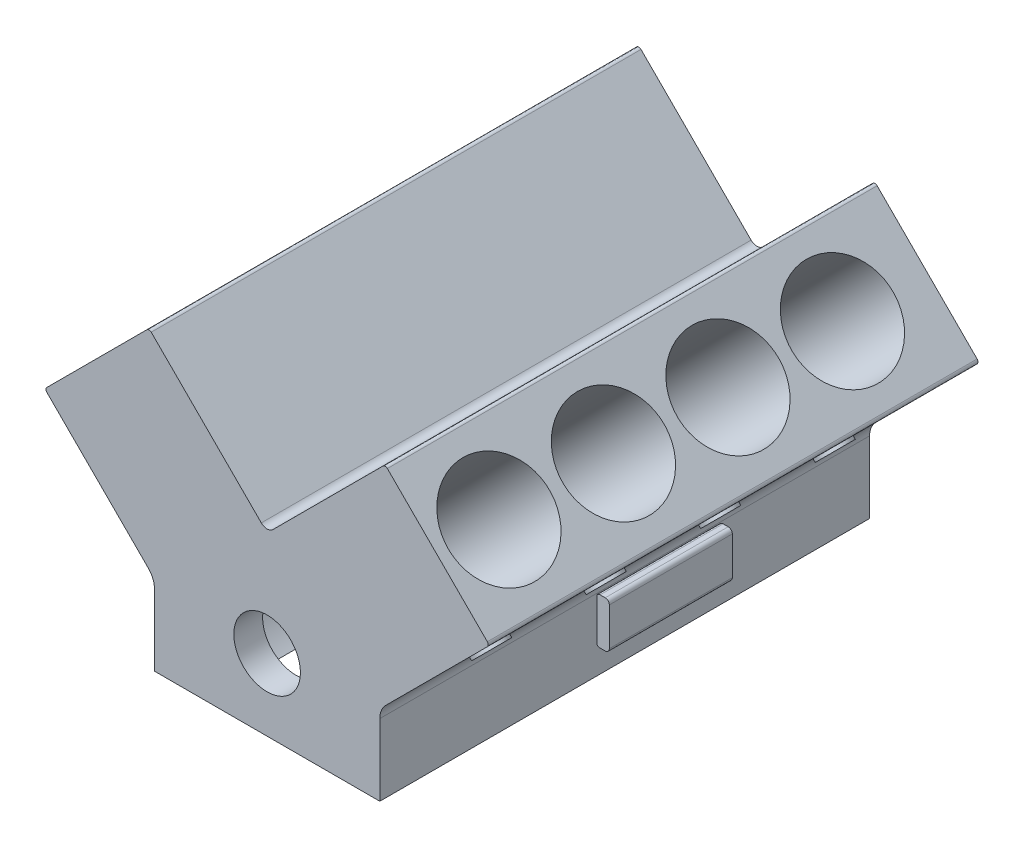
SolidWorks part; units mm, degrees
ref_plane "Front Plane" through (0, 0, 0) normal (0, 0, 1) x (1, 0, 0)
ref_plane "Top Plane" through (0, 0, 0) normal (0, 1, 0) x (1, 0, 0)
ref_plane "Right Plane" through (0, 0, 0) normal (1, 0, 0) x (0, 0, -1)
other "Configuration Table"
sketch "Sketch1" plane through (0, 0, 0) normal (0, 0, 1) x (1, 0, 0)
  line L0 (110, -70) -> (110, -0.1076)
  line L1 (115.8579, 14.0345) -> (214.9251, 113.1017)
  line L2 (214.9251, 117.3444) -> (117.3444, 214.9251)
  line L3 (113.1017, 214.9251) -> (5.6569, 107.4802)
  line L4 (-5.6569, 107.4802) -> (-113.1017, 214.9251)
  line L5 (-117.3444, 214.9251) -> (-214.9251, 117.3444)
  line L6 (-214.9251, 113.1017) -> (-115.8579, 14.0345)
  line L7 (-110, -0.1076) -> (-110, -70)
  line L8 (-110, -70) -> (110, -70)
  arc A0 (110, -0.1076) -> (115.8579, 14.0345) centre (130, -0.1076) cw
  arc A1 (214.9251, 113.1017) -> (214.9251, 117.3444) centre (212.8038, 115.223) ccw
  arc A2 (117.3444, 214.9251) -> (113.1017, 214.9251) centre (115.223, 212.8038) ccw
  arc A3 (5.6569, 107.4802) -> (-5.6569, 107.4802) centre (0, 113.1371) cw
  arc A4 (-113.1017, 214.9251) -> (-117.3444, 214.9251) centre (-115.223, 212.8038) ccw
  arc A5 (-214.9251, 117.3444) -> (-214.9251, 113.1017) centre (-212.8038, 115.223) ccw
  arc A6 (-115.8579, 14.0345) -> (-110, -0.1076) centre (-130, -0.1076) cw
extrude "Block Casting" add sketch "Sketch1" along normal blind 478 from offset 406 offset against normal yes
sketch "Sketch2" plane through (0, 0, 0) normal (0, 0, 1) x (1, 0, 0)
  line L0 (113, -45) -> (118, -45)
  line L1 (122, -41) -> (122, -4)
  line L2 (118, 0) -> (113, 0)
  line L3 (109, -4) -> (109, -41)
  line L4 (-109, -41) -> (-109, -4)
  line L5 (-113, 0) -> (-118, 0)
  line L6 (-122, -4) -> (-122, -41)
  line L7 (-118, -45) -> (-113, -45)
  arc A0 (109, -41) -> (113, -45) centre (113, -41) ccw
  arc A1 (118, -45) -> (122, -41) centre (118, -41) ccw
  arc A2 (122, -4) -> (118, 0) centre (118, -4) ccw
  arc A3 (113, 0) -> (109, -4) centre (113, -4) ccw
  arc A4 (-113, -45) -> (-109, -41) centre (-113, -41) ccw
  arc A5 (-109, -4) -> (-113, 0) centre (-113, -4) ccw
  arc A6 (-118, 0) -> (-122, -4) centre (-118, -4) ccw
  arc A7 (-122, -41) -> (-118, -45) centre (-118, -41) ccw
extrude "Engine Mount Pads" add sketch "Sketch2" along normal blind 120 from offset 260 offset against normal yes
sketch "Sketch3" plane through (0, 0, 0) normal (0, 0, 1) x (1, 0, 0)
  circle A0 centre (0, 0) radius 92
extrude "Crankcase Bay 1" cut sketch "Sketch3" along normal blind 87.76 from offset 43.88 offset against normal yes
sketch "Sketch4" plane through (0, 0, 0) normal (0, 0, 1) x (1, 0, 0)
  circle A0 centre (0, 0) radius 92
extrude "Crankcase Bay 2" cut sketch "Sketch4" along normal blind 87.76 from offset 155.64 offset against normal yes
sketch "Sketch5" plane through (0, 0, 0) normal (0, 0, 1) x (1, 0, 0)
  circle A0 centre (0, 0) radius 92
extrude "Crankcase Bay 3" cut sketch "Sketch5" along normal blind 87.76 from offset 267.4 offset against normal yes
sketch "Sketch6" plane through (0, 0, 0) normal (0, 0, 1) x (1, 0, 0)
  circle A0 centre (0, 0) radius 92
extrude "Crankcase Bay 4" cut sketch "Sketch6" along normal blind 87.76 from offset 379.16 offset against normal yes
sketch "Sketch7" plane through (0, 0, 0) normal (0, 0, 1) x (1, 0, 0)
  circle A0 centre (0, 0) radius 32.5
extrude "Main Bearing Bore" cut sketch "Sketch7" against normal through all and the other way through all
sketch "Sketch8" plane through (166.1347, 166.1347, 0) normal (0.7071, 0.7071, 0) x (0, 0, -1)
  circle A0 centre (-11.9, 0) radius 49.5
  circle A1 centre (99.86, 0) radius 49.5
  circle A2 centre (211.62, 0) radius 49.5
  circle A3 centre (323.38, 0) radius 49.5
extrude "Cylinder Bores Left" cut sketch "Sketch8" against normal blind 174.95
sketch "Sketch9" plane through (50.9117, -50.9117, 0) normal (0.7071, -0.7071, 0) x (0, 0, -1)
  circle A0 centre (-11.9, 150) radius 16
  circle A1 centre (99.86, 150) radius 16
  circle A2 centre (211.62, 150) radius 16
  circle A3 centre (323.38, 150) radius 16
extrude "Core Plugs Left" add sketch "Sketch9" along normal blind 3
sketch "Sketch10" plane through (-166.1347, 166.1347, 0) normal (-0.7071, 0.7071, 0) x (0, 0, 1)
  circle A0 centre (-11.9, 0) radius 49.5
  circle A1 centre (-123.66, 0) radius 49.5
  circle A2 centre (-235.42, 0) radius 49.5
  circle A3 centre (-347.18, 0) radius 49.5
extrude "Cylinder Bores Right" cut sketch "Sketch10" against normal blind 174.95
sketch "Sketch11" plane through (-50.9117, -50.9117, 0) normal (-0.7071, -0.7071, 0) x (0, 0, 1)
  circle A0 centre (-11.9, 150) radius 16
  circle A1 centre (-123.66, 150) radius 16
  circle A2 centre (-235.42, 150) radius 16
  circle A3 centre (-347.18, 150) radius 16
extrude "Core Plugs Right" add sketch "Sketch11" along normal blind 3
ref_axis "Crank Axis" through (0, 0, -199.0801) along (0, 0, 1)
sketch3d "Bore Axis 1 Line"
  line L0 (0, 0, 11.9) -> (212.132, 212.132, 11.9)
ref_axis "Bore Axis 1" through (0, 0, 11.9) along (0.7071, 0.7071, 0)
ref_plane "Cylinder Plane 1" through (0, 0, 11.9) normal (0, 0, 1) x (1, 0, 0)
sketch3d "Bore Axis 2 Line"
  line L0 (0, 0, -11.9) -> (-212.132, 212.132, -11.9)
ref_axis "Bore Axis 2" through (0, 0, -11.9) along (-0.7071, 0.7071, 0)
ref_plane "Cylinder Plane 2" through (0, 0, -11.9) normal (0, 0, 1) x (1, 0, 0)
sketch3d "Bore Axis 3 Line"
  line L0 (0, 0, -99.86) -> (212.132, 212.132, -99.86)
ref_axis "Bore Axis 3" through (0, 0, -99.86) along (0.7071, 0.7071, 0)
ref_plane "Cylinder Plane 3" through (0, 0, -99.86) normal (0, 0, 1) x (1, 0, 0)
sketch3d "Bore Axis 4 Line"
  line L0 (0, 0, -123.66) -> (-212.132, 212.132, -123.66)
ref_axis "Bore Axis 4" through (0, 0, -123.66) along (-0.7071, 0.7071, 0)
ref_plane "Cylinder Plane 4" through (0, 0, -123.66) normal (0, 0, 1) x (1, 0, 0)
sketch3d "Bore Axis 5 Line"
  line L0 (0, 0, -211.62) -> (212.132, 212.132, -211.62)
ref_axis "Bore Axis 5" through (0, 0, -211.62) along (0.7071, 0.7071, 0)
ref_plane "Cylinder Plane 5" through (0, 0, -211.62) normal (0, 0, 1) x (1, 0, 0)
sketch3d "Bore Axis 6 Line"
  line L0 (0, 0, -235.42) -> (-212.132, 212.132, -235.42)
ref_axis "Bore Axis 6" through (0, 0, -235.42) along (-0.7071, 0.7071, 0)
ref_plane "Cylinder Plane 6" through (0, 0, -235.42) normal (0, 0, 1) x (1, 0, 0)
sketch3d "Bore Axis 7 Line"
  line L0 (0, 0, -323.38) -> (212.132, 212.132, -323.38)
ref_axis "Bore Axis 7" through (0, 0, -323.38) along (0.7071, 0.7071, 0)
ref_plane "Cylinder Plane 7" through (0, 0, -323.38) normal (0, 0, 1) x (1, 0, 0)
sketch3d "Bore Axis 8 Line"
  line L0 (0, 0, -347.18) -> (-212.132, 212.132, -347.18)
ref_axis "Bore Axis 8" through (0, 0, -347.18) along (-0.7071, 0.7071, 0)
ref_plane "Cylinder Plane 8" through (0, 0, -347.18) normal (0, 0, 1) x (1, 0, 0)
